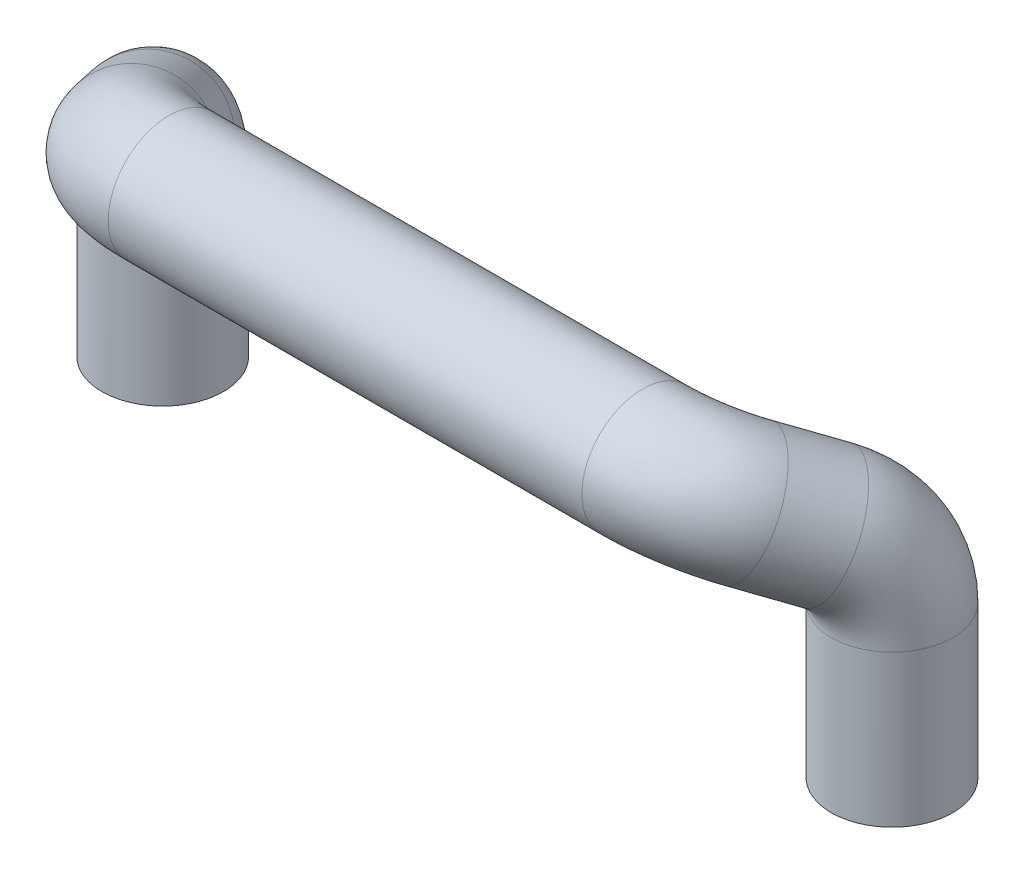
SolidWorks part; units mm, degrees
ref_plane "前视基准面" through (0, 0, 0) normal (0, 0, 1) x (1, 0, 0)
ref_plane "上视基准面" through (0, 0, 0) normal (0, 1, 0) x (1, 0, 0)
ref_plane "右视基准面" through (0, 0, 0) normal (1, 0, 0) x (0, 0, -1)
ref_axis "基准轴2" through (-88.99, 0, 0) along (1, 0, 0)
ref_plane "基准面5" through (0, 0, 0) normal (0, -0.866, 0.5) x (1, 0, 0)
sketch3d "3D草图8"
  line L0 (65, -25, 0) -> (65, -6.2902, 0)
  line L1 (61.8549, 2.7237, 4.7176) -> (57.8868, 6.1603, 10.6699)
  line L2 (49.2265, 8.6603, 15) -> (-9.2265, 8.6603, 15)
  line L3 (-17.8868, 6.1603, 10.6699) -> (-21.8549, 2.7237, 4.7176)
  line L4 (-25, -6.2902, 0) -> (-25, -25, 0)
  arc A0 (-9.2265, 8.6603, 15) -> (-17.8868, 6.1603, 10.6699) centre (-9.2265, 3.6603, 6.3397) ccw
  arc A1 (49.2265, 8.6603, 15) -> (57.8868, 6.1603, 10.6699) centre (49.2265, 3.6603, 6.3397) ccw
  arc A2 (65, -6.2902, 0) -> (61.8549, 2.7237, 4.7176) centre (59.453, -6.2902, 8.3205) ccw
  arc A3 (-25, -6.2902, 0) -> (-21.8549, 2.7237, 4.7176) centre (-19.453, -6.2902, 8.3205) ccw
  point P6 (0, 0, 0)
  point P8 (0, 0, 0)
  point P12 (-15, 8.6603, 15)
  point P13 (-9.2265, -5, 11.3397)
  point P16 (55, 8.6603, 15)
  point P17 (49.2265, 12.3205, 1.3397)
  point P20 (65, 0, 0)
  point P21 (67.7735, -6.2902, 13.8675)
  point P24 (-25, 0, 0)
  point P25 (-11.1325, -6.2902, 2.7735)
  dimension "D7" = 10
  dimension "D8" = 10
  dimension "D9" = 10
  dimension "D1" = 90
  dimension "D2" = 25
  dimension "D3" = 25
  dimension "D4" = 70
  dimension "D5" = 120
  dimension "D6" = 120
sweep "扫描8" add path "3D草图8" circular profile diameter 15 parameters "D3"=15
